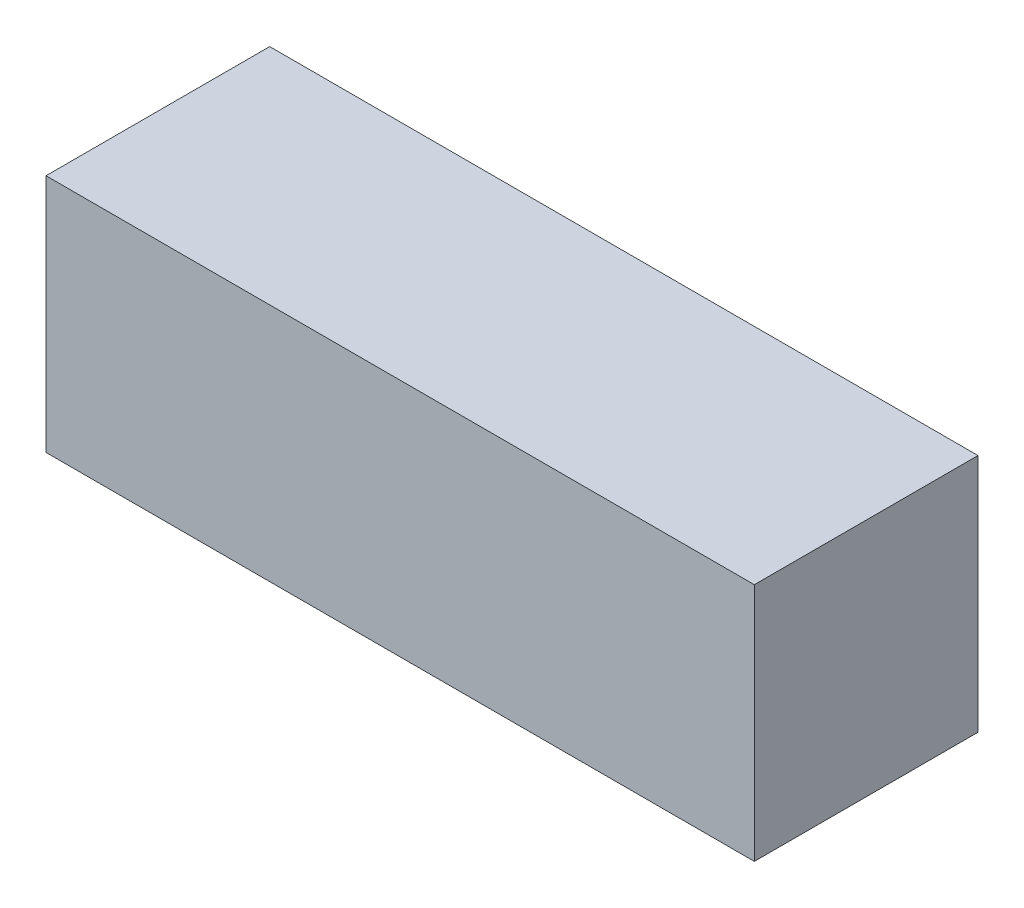
SolidWorks part; units mm, degrees
ref_plane "Front Plane" through (0, 0, 0) normal (0, 0, 1) x (1, 0, 0)
ref_plane "Top Plane" through (0, 0, 0) normal (0, 1, 0) x (1, 0, 0)
ref_plane "Right Plane" through (0, 0, 0) normal (1, 0, 0) x (0, 0, -1)
sketch "Sketch1" plane through (0, 0, 0) normal (0, 0, 1) x (1, 0, 0)
  line L1 (0, 0) -> (133, 0)
  line L2 (0, 0) -> (0, 45)
  line L3 (0, 45) -> (133, 45)
  line L4 (133, 0) -> (133, 45)
  dimension "D1" = 45
  dimension "D2" = 133
extrude "Boss-Extrude1" add sketch "Sketch1" along normal blind 42
sketch "Sketch2" plane through (0, 0, 0) normal (-1, 0, 0) x (0, 0, 1)
  line L0 (12, 14) -> (2, 14) construction
  line L1 (12, 31) -> (2, 31)
  line L2 (12, 31) -> (12, 14)
  line L3 (12, 14) -> (2, 14)
  line L4 (2, 31) -> (2, 14)
extrude "Cut-Extrude1" cut sketch "Sketch2" against normal blind 122
